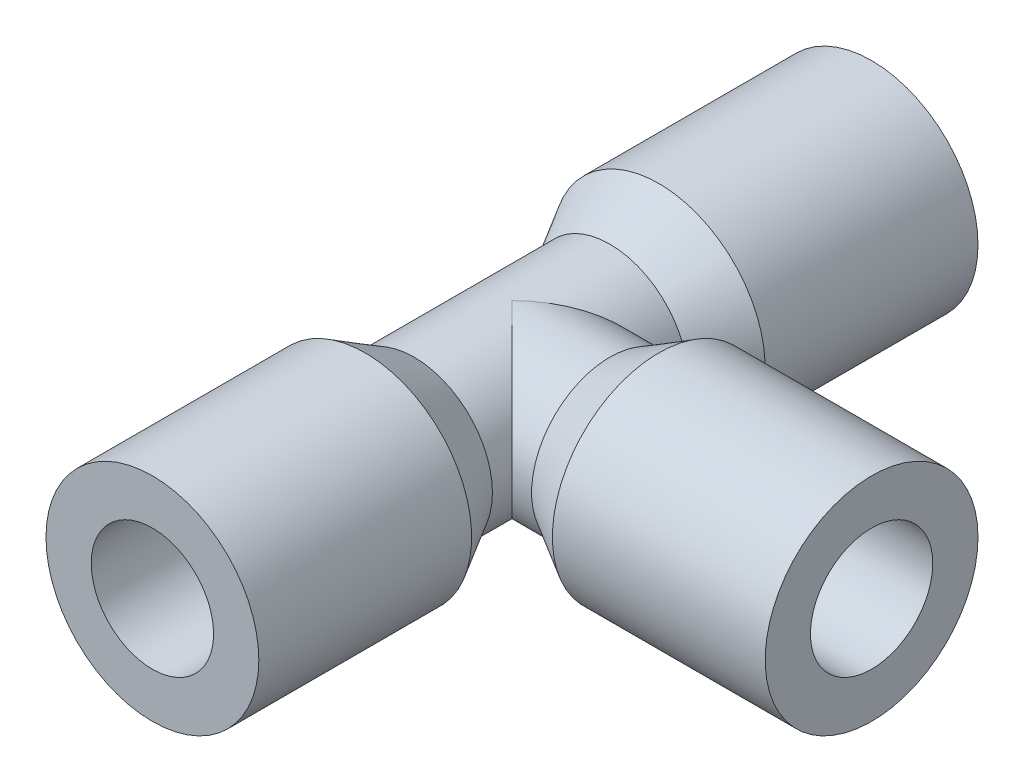
SolidWorks part; units mm, degrees
ref_plane "Front Plane" through (0, 0, 0) normal (0, 0, 1) x (1, 0, 0)
ref_plane "Top Plane" through (0, 0, 0) normal (0, 1, 0) x (1, 0, 0)
ref_plane "Right Plane" through (0, 0, 0) normal (1, 0, 0) x (0, 0, -1)
sketch "Sketch1" plane through (0, 0, 0) normal (0, 0, 1) x (1, 0, 0)
  circle A0 centre (0, 0) radius 5.5245
  dimension "D1" = 11.049
extrude "Boss-Extrude1" add sketch "Sketch1" along normal blind 11.049
ref_plane "Plane1" through (0, 0, 13.589) normal (0, 0, 1) x (1, 0, 0)
sketch "Sketch2" plane through (0, 0, 13.589) normal (0, 0, 1) x (1, 0, 0)
  circle A0 centre (0, 0) radius 4.064
  dimension "D1" = 8.128
extrude "Boss-Extrude2" add sketch "Sketch2" along normal blind 5.08 separate body
ref_plane "Plane2" through (0, 0, 18.669) normal (0, 0, 1) x (1, 0, 0)
ref_axis "Axis1" through (0, 0, -0.9335) along (0, 0, 1)
sketch "Sketch3" plane through (0, 0, 11.049) normal (0, 0, 1) x (1, 0, 0)
  circle A0 centre (0, 0) radius 5.5245 construction
  circle A1 centre (0, 0) radius 5.5245
sketch "Sketch4" plane through (0, 0, 13.589) normal (0, 0, 1) x (1, 0, 0)
  circle A0 centre (0, 0) radius 4.064 construction
  circle A1 centre (0, 0) radius 4.064
loft "Loft2" add profiles "Sketch3", "Sketch4" connector at (5.5245, 0, 11.049) connector at (4.064, 0, 13.589)
mirror "Mirror5" about plane through (0, 0, 18.669) normal (0, 0, 1) of "Boss-Extrude2", "Loft2", "Boss-Extrude1"
ref_axis "Axis2" through (0, 6.077, 18.669) along (0, -1, 0)
sketch "Sketch5" plane through (0, 0, 0) normal (1, 0, 0) x (0, 0, -1)
  line L2 (-18.669, 55) -> (-18.669, -55) construction
  circle A0 centre (-18.669, 0) radius 4.064
  dimension "D1" = 8.128
extrude "Boss-Extrude3" add sketch "Sketch5" along normal blind 5.08
ref_plane "Plane3" through (7.62, 0, 0) normal (1, 0, 0) x (0, 0, -1)
sketch "Sketch6" plane through (7.62, 0, 0) normal (1, 0, 0) x (0, 0, -1)
  circle A0 centre (-18.669, 0) radius 5.5245
  circle A1 centre (-18.669, 0) radius 4.064 construction
  dimension "D1" = 11.049
extrude "Boss-Extrude4" add sketch "Sketch6" along normal blind 11.049 separate body
loft "Loft3" add section edge at (5.08, 0, 14.605) section edge at (7.62, 0, 13.1445)
sketch "Sketch7" plane through (18.669, 0, 0) normal (1, 0, 0) x (0, 0, -1)
  circle A0 centre (-18.669, 0) radius 3.175
  circle A1 centre (-18.669, 0) radius 5.5245 construction
  dimension "D1" = 6.35
extrude "Cut-Extrude1" cut sketch "Sketch7" against normal blind 16.891
sketch "Sketch9" plane through (0, 0, 0) normal (0, 0, -1) x (-1, 0, 0)
  circle A0 centre (0, 0) radius 3.175
  dimension "D1" = 6.35
extrude "Cut-Extrude2" cut sketch "Sketch9" against normal blind 49.403
